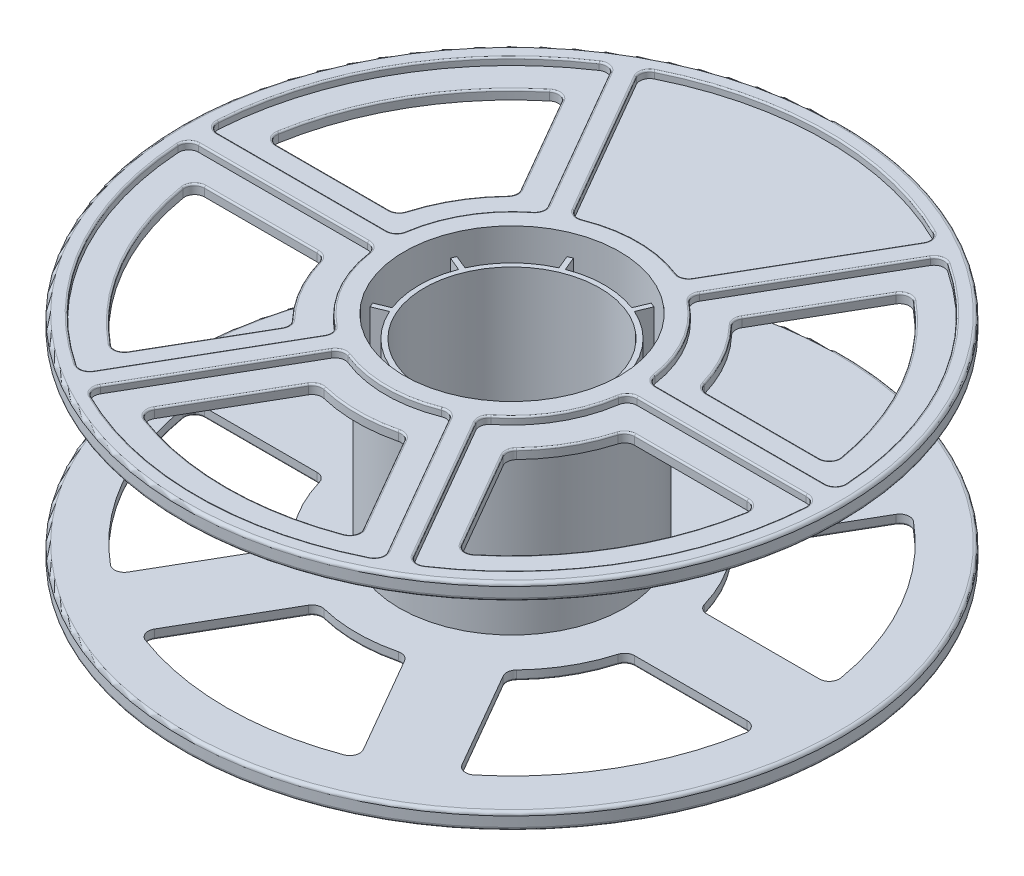
SolidWorks part; units mm, degrees
ref_plane "Front Plane" through (0, 0, 0) normal (0, 0, 1) x (1, 0, 0)
ref_plane "Top Plane" through (0, 0, 0) normal (0, 1, 0) x (1, 0, 0)
ref_plane "Right Plane" through (0, 0, 0) normal (1, 0, 0) x (0, 0, -1)
sketch "Sketch2" plane through (0, 0, 0) normal (0, 0, 1) x (1, 0, 0)
  line L0 (26.5, -26) -> (26.5, 26)
  line L1 (26.5, 26) -> (28, 26)
  line L2 (26.5, -26) -> (28, -26)
  line L3 (28, 26) -> (28, -26)
  line L4 (0, 0) -> (26.5, 0) construction
  line L5 (0, -1000) -> (0, 49000) construction
  point P3 (26.5, 0)
  dimension "D1" = 26.5
  dimension "D2" = 1.5
  dimension "D3" = 52
revolve "Inner Ring" add sketch "Sketch2" angle 360 about L5
sketch "Sketch3" plane through (0, 26, 0) normal (0, 1, 0) x (1, 0, 0)
  line L0 (0, 0) -> (0, 32.5) construction
  line L3 (11.741, 30.3051) -> (10.0184, 26.1464)
  line L4 (0, 0) -> (12.4372, 30.0261) construction
  line L5 (13.1268, 29.7311) -> (11.4042, 25.5723)
  line L6 (9.9856, 26.0672) -> (11.3714, 25.4932) construction
  line L7 (29.7311, 13.1268) -> (25.5723, 11.4042)
  line L8 (30.3051, 11.741) -> (26.1464, 10.0184)
  line L9 (25.4932, 11.3714) -> (26.0672, 9.9856) construction
  line L10 (30.3051, -11.741) -> (26.1464, -10.0184)
  line L11 (29.7311, -13.1268) -> (25.5723, -11.4042)
  line L12 (26.0672, -9.9856) -> (25.4932, -11.3714) construction
  line L13 (13.1268, -29.7311) -> (11.4042, -25.5723)
  line L14 (11.741, -30.3051) -> (10.0184, -26.1464)
  line L15 (11.3714, -25.4932) -> (9.9856, -26.0672) construction
  line L16 (-11.741, -30.3051) -> (-10.0184, -26.1464)
  line L17 (-13.1268, -29.7311) -> (-11.4042, -25.5723)
  line L18 (-9.9856, -26.0672) -> (-11.3714, -25.4932) construction
  line L19 (-29.7311, -13.1268) -> (-25.5723, -11.4042)
  line L20 (-30.3051, -11.741) -> (-26.1464, -10.0184)
  line L21 (-25.4932, -11.3714) -> (-26.0672, -9.9856) construction
  line L22 (-30.3051, 11.741) -> (-26.1464, 10.0184)
  line L23 (-29.7311, 13.1268) -> (-25.5723, 11.4042)
  line L24 (-26.0672, 9.9856) -> (-25.4932, 11.3714) construction
  line L25 (-13.1268, 29.7311) -> (-11.4042, 25.5723)
  line L26 (-11.741, 30.3051) -> (-10.0184, 26.1464)
  line L27 (-11.3714, 25.4932) -> (-9.9856, 26.0672) construction
  circle A0 centre (0, 0) radius 32.5 construction
  circle A1 centre (0, 0) radius 28 construction
  circle A3 centre (0, 0) radius 28 construction
  arc A5 (11.741, 30.3051) -> (13.1268, 29.7311) centre (0, 0) cw
  arc A6 (10.0184, 26.1464) -> (11.4042, 25.5723) centre (0, 0) cw
  arc A7 (29.7311, 13.1268) -> (30.3051, 11.741) centre (0, 0) cw
  arc A8 (25.5723, 11.4042) -> (26.1464, 10.0184) centre (0, 0) cw
  arc A9 (30.3051, -11.741) -> (29.7311, -13.1268) centre (0, 0) cw
  arc A10 (26.1464, -10.0184) -> (25.5723, -11.4042) centre (0, 0) cw
  arc A11 (13.1268, -29.7311) -> (11.741, -30.3051) centre (0, 0) cw
  arc A12 (11.4042, -25.5723) -> (10.0184, -26.1464) centre (0, 0) cw
  arc A13 (-11.741, -30.3051) -> (-13.1268, -29.7311) centre (0, 0) cw
  arc A14 (-10.0184, -26.1464) -> (-11.4042, -25.5723) centre (0, 0) cw
  arc A15 (-29.7311, -13.1268) -> (-30.3051, -11.741) centre (0, 0) cw
  arc A16 (-25.5723, -11.4042) -> (-26.1464, -10.0184) centre (0, 0) cw
  arc A17 (-30.3051, 11.741) -> (-29.7311, 13.1268) centre (0, 0) cw
  arc A18 (-26.1464, 10.0184) -> (-25.5723, 11.4042) centre (0, 0) cw
  arc A19 (-13.1268, 29.7311) -> (-11.741, 30.3051) centre (0, 0) cw
  arc A20 (-11.4042, 25.5723) -> (-10.0184, 26.1464) centre (0, 0) cw
  point P15 (10.6785, 25.7802)
  point P26 (25.7802, 10.6785)
  point P33 (25.7802, -10.6785)
  point P40 (10.6785, -25.7802)
  point P47 (-10.6785, -25.7802)
  point P54 (-25.7802, -10.6785)
  point P61 (-25.7802, 10.6785)
  point P68 (-10.6785, 25.7802)
  dimension "D1" = 65
  dimension "D2" = 22.5
  dimension "D3" = 1.5
  dimension "D4" = 8
extrude "Inner Ring Ribs" add sketch "Sketch3" against normal up to surface (52 mm away) up to face at (28, -26, 0)
sketch "Sketch4" plane through (0, 0, 0) normal (0, 0, 1) x (1, 0, 0)
  line L0 (0, 0) -> (32.5, 0) construction
  line L1 (32.5, 32.5) -> (32.5, -32.5)
  line L3 (34, 27.5) -> (34, -27.5)
  line L6 (99.5, -32.5) -> (99.5, -27.5)
  line L7 (99.5, -27.5) -> (34, -27.5)
  line L8 (32.5, 32.5) -> (99.5, 32.5)
  line L9 (99.5, 32.5) -> (99.5, 27.5)
  line L10 (99.5, 27.5) -> (34, 27.5)
  line L11 (32.5, -32.5) -> (99.5, -32.5)
  line L12 (0, -1000) -> (0, 49000) construction
  point P6 (32.5, 0)
  dimension "D1" = 65
  dimension "D3" = 32.5
  dimension "D2" = 1.5
  dimension "D4" = 5
  dimension "D5" = 5
  dimension "D6" = 99.5
revolve "Spool Panels" add sketch "Sketch4" angle 360 about L12
sketch "Sketch5" plane through (0, 32.5, 0) normal (0, 1, 0) x (1, 0, 0)
  line L0 (0, 0) -> (0, 99.5) construction
  line L1 (0, 0) -> (49.75, 86.1695) construction
  line L2 (0, 0) -> (-49.75, 86.1695) construction
  line L3 (31.0626, 59.602) -> (36.0856, 56.702) construction
  line L4 (-41.7223, 66.4651) -> (-36.6993, 69.3651) construction
  line L6 (43.3437, 80.8735) -> (17.8257, 36.675)
  line L7 (-43.3437, 80.8735) -> (-17.8257, 36.675)
  line L19 (91.7104, 2.9) -> (40.6743, 2.9)
  line L20 (48.3667, 77.9735) -> (22.8486, 33.775)
  line L21 (48.3667, -77.9735) -> (22.8486, -33.775)
  line L22 (91.7104, -2.9) -> (40.6743, -2.9)
  line L23 (-43.3437, -80.8735) -> (-17.8257, -36.675)
  line L24 (43.3437, -80.8735) -> (17.8257, -36.675)
  line L25 (-91.7104, -2.9) -> (-40.6743, -2.9)
  line L26 (-48.3667, -77.9735) -> (-22.8486, -33.775)
  line L27 (-48.3667, 77.9735) -> (-22.8486, 33.775)
  line L28 (-91.7104, 2.9) -> (-40.6743, 2.9)
  circle A0 centre (0, 0) radius 32.5 construction
  circle A1 centre (0, 0) radius 32.5 construction
  arc A2 (14.1161, 35.3885) -> (-14.1161, 35.3885) centre (0, 0) ccw
  circle A3 centre (0, 0) radius 99.5 construction
  arc A6 (42.0758, 85.0626) -> (-42.0758, 85.0626) centre (0, 0) ccw
  arc A8 (-17.8257, 36.675) -> (-14.1161, 35.3885) centre (-15.2276, 38.175) ccw
  arc A9 (17.8257, 36.675) -> (14.1161, 35.3885) centre (15.2276, 38.175) cw
  arc A10 (43.3437, 80.8735) -> (42.0758, 85.0626) centre (40.7457, 82.3735) ccw
  arc A11 (-43.3437, 80.8735) -> (-42.0758, 85.0626) centre (-40.7457, 82.3735) cw
  circle A42 centre (0, 0) radius 99.5 construction
  arc A43 (91.7104, 2.9) -> (94.7042, 6.0926) centre (91.7104, 5.9) ccw
  arc A44 (40.6743, 2.9) -> (37.7054, 5.4693) centre (40.6743, 5.9) cw
  arc A45 (37.7054, 5.4693) -> (23.5893, 29.9192) centre (0, 0) ccw
  arc A46 (22.8486, 33.775) -> (23.5893, 29.9192) centre (25.4467, 32.275) ccw
  arc A47 (48.3667, 77.9735) -> (52.6285, 78.97) centre (50.9648, 76.4735) cw
  arc A48 (94.7042, 6.0926) -> (52.6285, 78.97) centre (0, 0) ccw
  arc A49 (48.3667, -77.9735) -> (52.6285, -78.97) centre (50.9648, -76.4735) ccw
  arc A50 (22.8486, -33.775) -> (23.5893, -29.9192) centre (25.4467, -32.275) cw
  arc A51 (23.5893, -29.9192) -> (37.7054, -5.4693) centre (0, 0) ccw
  arc A52 (40.6743, -2.9) -> (37.7054, -5.4693) centre (40.6743, -5.9) ccw
  arc A53 (91.7104, -2.9) -> (94.7042, -6.0926) centre (91.7104, -5.9) cw
  arc A54 (52.6285, -78.97) -> (94.7042, -6.0926) centre (0, 0) ccw
  arc A55 (-43.3437, -80.8735) -> (-42.0758, -85.0626) centre (-40.7457, -82.3735) ccw
  arc A56 (-17.8257, -36.675) -> (-14.1161, -35.3885) centre (-15.2276, -38.175) cw
  arc A57 (-14.1161, -35.3885) -> (14.1161, -35.3885) centre (0, 0) ccw
  arc A58 (17.8257, -36.675) -> (14.1161, -35.3885) centre (15.2276, -38.175) ccw
  arc A59 (43.3437, -80.8735) -> (42.0758, -85.0626) centre (40.7457, -82.3735) cw
  arc A60 (-42.0758, -85.0626) -> (42.0758, -85.0626) centre (0, 0) ccw
  arc A61 (-91.7104, -2.9) -> (-94.7042, -6.0926) centre (-91.7104, -5.9) ccw
  arc A62 (-40.6743, -2.9) -> (-37.7054, -5.4693) centre (-40.6743, -5.9) cw
  arc A63 (-37.7054, -5.4693) -> (-23.5893, -29.9192) centre (0, 0) ccw
  arc A64 (-22.8486, -33.775) -> (-23.5893, -29.9192) centre (-25.4467, -32.275) ccw
  arc A65 (-48.3667, -77.9735) -> (-52.6285, -78.97) centre (-50.9648, -76.4735) cw
  arc A66 (-94.7042, -6.0926) -> (-52.6285, -78.97) centre (0, 0) ccw
  arc A67 (-48.3667, 77.9735) -> (-52.6285, 78.97) centre (-50.9648, 76.4735) ccw
  arc A68 (-22.8486, 33.775) -> (-23.5893, 29.9192) centre (-25.4467, 32.275) cw
  arc A69 (-23.5893, 29.9192) -> (-37.7054, 5.4693) centre (0, 0) ccw
  arc A70 (-40.6743, 2.9) -> (-37.7054, 5.4693) centre (-40.6743, 5.9) ccw
  arc A71 (-91.7104, 2.9) -> (-94.7042, 6.0926) centre (-91.7104, 5.9) cw
  arc A72 (-52.6285, 78.97) -> (-94.7042, 6.0926) centre (0, 0) ccw
  point P14 (33.5741, 58.152)
  point P17 (-39.2108, 67.9151)
  point P39 (44.9164, 83.5974)
  dimension "D1" = 5.6
  dimension "D4" = 4.6
  dimension "D7" = 3
  dimension "D8" = 6
  dimension "D2" = 30
  dimension "D3" = 30
  dimension "D5" = 5.8
  dimension "D6" = 5.8
extrude "Top Panel Inset" cut sketch "Sketch5" against normal blind 2.2
sketch "Sketch7" plane through (0, -32.5, 0) normal (0, -1, 0) x (1, 0, 0)
  line L0 (0, 0) -> (0, 99.5) construction
  line L1 (0, 0) -> (49.75, 86.1695) construction
  line L2 (0, 0) -> (-49.75, 86.1695) construction
  line L3 (31.0626, 59.602) -> (36.0856, 56.702) construction
  line L4 (-41.7223, 66.4651) -> (-36.6993, 69.3651) construction
  line L5 (43.3437, 80.8735) -> (17.8257, 36.675)
  line L6 (-43.3437, 80.8735) -> (-17.8257, 36.675)
  line L7 (91.7104, 2.9) -> (40.6743, 2.9)
  line L8 (48.3667, 77.9735) -> (22.8486, 33.775)
  line L9 (48.3667, -77.9735) -> (22.8486, -33.775)
  line L10 (91.7104, -2.9) -> (40.6743, -2.9)
  line L11 (-43.3437, -80.8735) -> (-17.8257, -36.675)
  line L12 (43.3437, -80.8735) -> (17.8257, -36.675)
  line L13 (-91.7104, -2.9) -> (-40.6743, -2.9)
  line L14 (-48.3667, -77.9735) -> (-22.8486, -33.775)
  line L15 (-48.3667, 77.9735) -> (-22.8486, 33.775)
  line L16 (-91.7104, 2.9) -> (-40.6743, 2.9)
  circle A0 centre (0, 0) radius 32.5 construction
  arc A1 (14.1161, 35.3885) -> (-14.1161, 35.3885) centre (0, 0) ccw
  arc A2 (42.0758, 85.0626) -> (-42.0758, 85.0626) centre (0, 0) ccw
  arc A3 (-17.8257, 36.675) -> (-14.1161, 35.3885) centre (-15.2276, 38.175) ccw
  arc A4 (17.8257, 36.675) -> (14.1161, 35.3885) centre (15.2276, 38.175) cw
  arc A5 (43.3437, 80.8735) -> (42.0758, 85.0626) centre (40.7457, 82.3735) ccw
  arc A6 (-43.3437, 80.8735) -> (-42.0758, 85.0626) centre (-40.7457, 82.3735) cw
  circle A7 centre (0, 0) radius 99.5 construction
  arc A8 (91.7104, 2.9) -> (94.7042, 6.0926) centre (91.7104, 5.9) ccw
  arc A9 (40.6743, 2.9) -> (37.7054, 5.4693) centre (40.6743, 5.9) cw
  arc A10 (37.7054, 5.4693) -> (23.5893, 29.9192) centre (0, 0) ccw
  arc A11 (22.8486, 33.775) -> (23.5893, 29.9192) centre (25.4467, 32.275) ccw
  arc A12 (48.3667, 77.9735) -> (52.6285, 78.97) centre (50.9648, 76.4735) cw
  arc A13 (94.7042, 6.0926) -> (52.6285, 78.97) centre (0, 0) ccw
  arc A14 (48.3667, -77.9735) -> (52.6285, -78.97) centre (50.9648, -76.4735) ccw
  arc A15 (22.8486, -33.775) -> (23.5893, -29.9192) centre (25.4467, -32.275) cw
  arc A16 (23.5893, -29.9192) -> (37.7054, -5.4693) centre (0, 0) ccw
  arc A17 (40.6743, -2.9) -> (37.7054, -5.4693) centre (40.6743, -5.9) ccw
  arc A18 (91.7104, -2.9) -> (94.7042, -6.0926) centre (91.7104, -5.9) cw
  arc A19 (52.6285, -78.97) -> (94.7042, -6.0926) centre (0, 0) ccw
  arc A20 (-43.3437, -80.8735) -> (-42.0758, -85.0626) centre (-40.7457, -82.3735) ccw
  arc A21 (-17.8257, -36.675) -> (-14.1161, -35.3885) centre (-15.2276, -38.175) cw
  arc A22 (-14.1161, -35.3885) -> (14.1161, -35.3885) centre (0, 0) ccw
  arc A23 (17.8257, -36.675) -> (14.1161, -35.3885) centre (15.2276, -38.175) ccw
  arc A24 (43.3437, -80.8735) -> (42.0758, -85.0626) centre (40.7457, -82.3735) cw
  arc A25 (-42.0758, -85.0626) -> (42.0758, -85.0626) centre (0, 0) ccw
  arc A26 (-91.7104, -2.9) -> (-94.7042, -6.0926) centre (-91.7104, -5.9) ccw
  arc A27 (-40.6743, -2.9) -> (-37.7054, -5.4693) centre (-40.6743, -5.9) cw
  arc A28 (-37.7054, -5.4693) -> (-23.5893, -29.9192) centre (0, 0) ccw
  arc A29 (-22.8486, -33.775) -> (-23.5893, -29.9192) centre (-25.4467, -32.275) ccw
  arc A30 (-48.3667, -77.9735) -> (-52.6285, -78.97) centre (-50.9648, -76.4735) cw
  arc A31 (-94.7042, -6.0926) -> (-52.6285, -78.97) centre (0, 0) ccw
  arc A32 (-48.3667, 77.9735) -> (-52.6285, 78.97) centre (-50.9648, 76.4735) ccw
  arc A33 (-22.8486, 33.775) -> (-23.5893, 29.9192) centre (-25.4467, 32.275) cw
  arc A34 (-23.5893, 29.9192) -> (-37.7054, 5.4693) centre (0, 0) ccw
  arc A35 (-40.6743, 2.9) -> (-37.7054, 5.4693) centre (-40.6743, 5.9) ccw
  arc A36 (-91.7104, 2.9) -> (-94.7042, 6.0926) centre (-91.7104, 5.9) cw
  arc A37 (-52.6285, 78.97) -> (-94.7042, 6.0926) centre (0, 0) ccw
  point P11 (33.5741, 58.152)
  point P14 (-39.2108, 67.9151)
extrude "Bottom Panel Inset" cut sketch "Sketch7" against normal blind 2.2
sketch "Sketch8" plane through (0, 30.3, 0) normal (0, 1, 0) x (1, 0, 0)
  line L0 (17.8257, 36.675) -> (43.3437, 80.8735) construction
  line L1 (-43.3437, 80.8735) -> (-17.8257, 36.675) construction
  line L2 (17.8257, 36.675) -> (43.3437, 80.8735) construction
  line L3 (-43.3437, 80.8735) -> (-17.8257, 36.675) construction
  line L4 (-31.5249, 76.4028) -> (-14.5228, 46.9542)
  line L5 (14.5228, 46.9542) -> (31.5249, 76.4028)
  line L6 (-36.4155, 84.8735) -> (-10.8975, 40.675) construction
  line L7 (10.8975, 40.675) -> (36.4155, 84.8735) construction
  line L8 (50.4043, 65.5028) -> (33.4021, 36.0542)
  line L9 (47.9249, 10.9) -> (81.9292, 10.9)
  line L10 (81.9292, -10.9) -> (47.9249, -10.9)
  line L11 (33.4021, -36.0542) -> (50.4043, -65.5028)
  line L12 (31.5249, -76.4028) -> (14.5228, -46.9542)
  line L13 (-14.5228, -46.9542) -> (-31.5249, -76.4028)
  line L14 (-50.4043, -65.5028) -> (-33.4021, -36.0542)
  line L15 (-47.9249, -10.9) -> (-81.9292, -10.9)
  line L16 (-81.9292, 10.9) -> (-47.9249, 10.9)
  line L17 (-33.4021, 36.0542) -> (-50.4043, 65.5028)
  arc A0 (42.0758, 85.0626) -> (-42.0758, 85.0626) centre (0, 0) ccw construction
  arc A1 (14.1161, 35.3885) -> (-14.1161, 35.3885) centre (0, 0) ccw construction
  arc A2 (42.0758, 85.0626) -> (-42.0758, 85.0626) centre (0, 0) ccw construction
  arc A3 (14.1161, 35.3885) -> (-14.1161, 35.3885) centre (0, 0) ccw construction
  arc A4 (11.2078, 45.5411) -> (-11.2078, 45.5411) centre (0, 0) ccw
  arc A5 (29.9712, 80.7152) -> (-29.9712, 80.7152) centre (0, 0) ccw
  arc A6 (38.1741, 77.1748) -> (-38.1741, 77.1748) centre (0, 0) ccw construction
  arc A7 (17.3765, 43.5622) -> (-17.3765, 43.5622) centre (0, 0) ccw construction
  arc A8 (-14.5228, 46.9542) -> (-11.2078, 45.5411) centre (-11.9247, 48.4542) ccw
  arc A9 (11.2078, 45.5411) -> (14.5228, 46.9542) centre (11.9247, 48.4542) ccw
  arc A10 (31.5249, 76.4028) -> (29.9712, 80.7152) centre (28.9269, 77.9028) ccw
  arc A11 (-29.9712, 80.7152) -> (-31.5249, 76.4028) centre (-28.9269, 77.9028) ccw
  arc A12 (54.9158, 66.3134) -> (50.4043, 65.5028) centre (53.0024, 64.0028) ccw
  arc A13 (33.4021, 36.0542) -> (33.8359, 32.4768) centre (36.0002, 34.5542) ccw
  arc A14 (45.0437, 13.0643) -> (33.8359, 32.4768) centre (0, 0) ccw
  arc A15 (45.0437, 13.0643) -> (47.9249, 10.9) centre (47.9249, 13.9) ccw
  arc A16 (81.9292, 10.9) -> (84.887, 14.4018) centre (81.9292, 13.9) ccw
  arc A17 (84.887, 14.4018) -> (54.9158, 66.3134) centre (0, 0) ccw
  arc A18 (84.887, -14.4018) -> (81.9292, -10.9) centre (81.9292, -13.9) ccw
  arc A19 (47.9249, -10.9) -> (45.0437, -13.0643) centre (47.9249, -13.9) ccw
  arc A20 (33.8359, -32.4768) -> (45.0437, -13.0643) centre (0, 0) ccw
  arc A21 (33.8359, -32.4768) -> (33.4021, -36.0542) centre (36.0002, -34.5542) ccw
  arc A22 (50.4043, -65.5028) -> (54.9158, -66.3134) centre (53.0024, -64.0028) ccw
  arc A23 (54.9158, -66.3134) -> (84.887, -14.4018) centre (0, 0) ccw
  arc A24 (29.9712, -80.7152) -> (31.5249, -76.4028) centre (28.9269, -77.9028) ccw
  arc A25 (14.5228, -46.9542) -> (11.2078, -45.5411) centre (11.9247, -48.4542) ccw
  arc A26 (-11.2078, -45.5411) -> (11.2078, -45.5411) centre (0, 0) ccw
  arc A27 (-11.2078, -45.5411) -> (-14.5228, -46.9542) centre (-11.9247, -48.4542) ccw
  arc A28 (-31.5249, -76.4028) -> (-29.9712, -80.7152) centre (-28.9269, -77.9028) ccw
  arc A29 (-29.9712, -80.7152) -> (29.9712, -80.7152) centre (0, 0) ccw
  arc A30 (-54.9158, -66.3134) -> (-50.4043, -65.5028) centre (-53.0024, -64.0028) ccw
  arc A31 (-33.4021, -36.0542) -> (-33.8359, -32.4768) centre (-36.0002, -34.5542) ccw
  arc A32 (-45.0437, -13.0643) -> (-33.8359, -32.4768) centre (0, 0) ccw
  arc A33 (-45.0437, -13.0643) -> (-47.9249, -10.9) centre (-47.9249, -13.9) ccw
  arc A34 (-81.9292, -10.9) -> (-84.887, -14.4018) centre (-81.9292, -13.9) ccw
  arc A35 (-84.887, -14.4018) -> (-54.9158, -66.3134) centre (0, 0) ccw
  arc A36 (-84.887, 14.4018) -> (-81.9292, 10.9) centre (-81.9292, 13.9) ccw
  arc A37 (-47.9249, 10.9) -> (-45.0437, 13.0643) centre (-47.9249, 13.9) ccw
  arc A38 (-33.8359, 32.4768) -> (-45.0437, 13.0643) centre (0, 0) ccw
  arc A39 (-33.8359, 32.4768) -> (-33.4021, 36.0542) centre (-36.0002, 34.5542) ccw
  arc A40 (-50.4043, 65.5028) -> (-54.9158, 66.3134) centre (-53.0024, 64.0028) ccw
  arc A41 (-54.9158, 66.3134) -> (-84.887, 14.4018) centre (0, 0) ccw
  dimension "D4" = 3
  dimension "D1" = 8
  dimension "D2" = 8.8
  dimension "D3" = 8.8
  dimension "D5" = 6
extrude "Panel Cutouts" cut sketch "Sketch8" against normal through all contours L8 A13 A14 A15 L9 A16 A17 A12 | L10 A19 A20 A21 L11 A22 A23 A18 | L12 A25 A26 A27 L13 A28 A29 A24 | L14 A31 A32 A33 L15 A34 A35 A30 | L16 A37 A38 A39 L17 A40 A41 A36
fillet "Upper Edge Fillet" radius 0.5 96 edges at (93.8988, 32.5, 3.8479) (82.1858, 32.5, 47.45) (50.2818, 32.5, 79.3948) (35.6077, 32.5, 55.8743) (22.5006, 32.5, 31.7091) (32.9956, 32.5, 19.05) (38.7112, 32.5, 3.6315) (-16.2106, 32.5, 35.3406) (0, 32.5, 38.1) (16.2106, 32.5, 35.3406) (30.5847, 32.5, 58.7743) (43.617, 32.5, 83.2427) (0, 32.5, 94.9) (-43.617, 32.5, 83.2427) (-38.7112, 32.5, 3.6315) (-32.9956, 32.5, 19.05) (-22.5006, 32.5, 31.7091) (-35.6077, 32.5, 55.8743) (-50.2818, 32.5, 79.3948) (-82.1858, 32.5, 47.45) (-93.8988, 32.5, 3.8479) (50.2818, 32.5, -79.3948) (82.1858, 32.5, -47.45) (93.8988, 32.5, -3.8479) (66.1924, 32.5, -2.9) (38.7112, 32.5, -3.6315) (32.9956, 32.5, -19.05) (22.5006, 32.5, -31.7091) (43.617, 32.5, -83.2427) (30.5847, 32.5, -58.7743) (16.2106, 32.5, -35.3406) (0, 32.5, -38.1) (-16.2106, 32.5, -35.3406) (-30.5847, 32.5, -58.7743) (-43.617, 32.5, -83.2427) (-50.2818, 32.5, -79.3948) (-35.6077, 32.5, -55.8743) (-22.5006, 32.5, -31.7091) (-32.9956, 32.5, -19.05) (-38.7112, 32.5, -3.6315) (-66.1924, 32.5, -2.9) (-93.8988, 32.5, -3.8479) (66.1924, 32.5, 2.9) (-30.5847, 32.5, 58.7743) (-66.1924, 32.5, 2.9) (35.6077, 32.5, -55.8743) (0, 32.5, -94.9) (-82.1858, 32.5, -47.45) (-38.7112, -32.5, 3.6315) (-66.1924, -32.5, 2.9) (-93.8988, -32.5, 3.8479) (-82.1858, -32.5, 47.45) (-50.2818, -32.5, 79.3948) (-35.6077, -32.5, 55.8743) (-22.5006, -32.5, 31.7091) (-22.5006, -32.5, -31.7091) (-35.6077, -32.5, -55.8743) (-50.2818, -32.5, -79.3948) (-82.1858, -32.5, -47.45) (-93.8988, -32.5, -3.8479) (-66.1924, -32.5, -2.9) (-38.7112, -32.5, -3.6315) (43.617, -32.5, -83.2427) (0, -32.5, -94.9) (-43.617, -32.5, -83.2427) (-30.5847, -32.5, -58.7743) (-16.2106, -32.5, -35.3406) (0, -32.5, -38.1) (16.2106, -32.5, -35.3406) (93.8988, -32.5, 3.8479) (66.1924, -32.5, 2.9) (38.7112, -32.5, 3.6315) (32.9956, -32.5, 19.05) (22.5006, -32.5, 31.7091) (35.6077, -32.5, 55.8743) (50.2818, -32.5, 79.3948) (16.2106, -32.5, 35.3406) (0, -32.5, 38.1) (-16.2106, -32.5, 35.3406) (-30.5847, -32.5, 58.7743) (-43.617, -32.5, 83.2427) (0, -32.5, 94.9) (43.617, -32.5, 83.2427) (50.2818, -32.5, -79.3948) (35.6077, -32.5, -55.8743) (22.5006, -32.5, -31.7091) (32.9956, -32.5, -19.05) (38.7112, -32.5, -3.6315) (66.1924, -32.5, -2.9) (93.8988, -32.5, -3.8479) (-32.9956, -32.5, 19.05) (-32.9956, -32.5, -19.05) (30.5847, -32.5, -58.7743) (82.1858, -32.5, 47.45) (30.5847, -32.5, 58.7743) (82.1858, -32.5, -47.45)
fillet "Outer Ring Fillet" radius 1 4 edges at (99.5, -27.5, 0) (99.5, 27.5, 0) (99.5, -32.5, 0) (99.5, 32.5, 0)
fillet "Panel Inset Fillet" radius 0.5 80 edges at (-84.2211, -30.3, 11.9642) (-74.5648, -30.3, 43.05) (-52.4719, -30.3, 66.9555) (-41.9032, -30.3, 50.7785) (-33.022, -30.3, 34.1931) (-40.6166, -30.3, 23.45) (-46.1231, -30.3, 11.5014) (-52.4719, -30.3, -66.9555) (-74.5648, -30.3, -43.05) (-84.2211, -30.3, -11.9642) (-64.9271, -30.3, -10.9) (-46.1231, -30.3, -11.5014) (-40.6166, -30.3, -23.45) (-33.022, -30.3, -34.1931) (13.1011, -30.3, 45.6945) (0, -30.3, 46.9) (-13.1011, -30.3, 45.6945) (-23.0239, -30.3, 61.6785) (-31.7493, -30.3, 78.9197) (0, -30.3, 86.1) (31.7493, -30.3, 78.9197) (46.1231, -30.3, 11.5014) (40.6166, -30.3, 23.45) (33.022, -30.3, 34.1931) (41.9032, -30.3, 50.7785) (52.4719, -30.3, 66.9555) (74.5648, -30.3, 43.05) (84.2211, -30.3, 11.9642) (52.4719, -30.3, -66.9555) (41.9032, -30.3, -50.7785) (33.022, -30.3, -34.1931) (40.6166, -30.3, -23.45) (46.1231, -30.3, -11.5014) (64.9271, -30.3, -10.9) (84.2211, -30.3, -11.9642) (-13.1011, 30.3, 45.6945) (-23.0239, 30.3, 61.6785) (-31.7493, 30.3, 78.9197) (0, 30.3, 86.1) (31.7493, 30.3, 78.9197) (23.0239, 30.3, 61.6785) (13.1011, 30.3, 45.6945) (-46.1231, 30.3, 11.5014) (-40.6166, 30.3, 23.45) (-33.022, 30.3, 34.1931) (-41.9032, 30.3, 50.7785) (-52.4719, 30.3, 66.9555) (-74.5648, 30.3, 43.05) (-84.2211, 30.3, 11.9642) (84.2211, 30.3, 11.9642) (74.5648, 30.3, 43.05) (52.4719, 30.3, 66.9555) (41.9032, 30.3, 50.7785) (33.022, 30.3, 34.1931) (40.6166, 30.3, 23.45) (46.1231, 30.3, 11.5014) (-33.022, 30.3, -34.1931) (-40.6166, 30.3, -23.45) (-46.1231, 30.3, -11.5014) (-64.9271, 30.3, -10.9) (-84.2211, 30.3, -11.9642) (-74.5648, 30.3, -43.05) (-52.4719, 30.3, -66.9555) (52.4719, 30.3, -66.9555) (74.5648, 30.3, -43.05) (84.2211, 30.3, -11.9642) (64.9271, 30.3, -10.9) (46.1231, 30.3, -11.5014) (40.6166, 30.3, -23.45) (33.022, 30.3, -34.1931) (-64.9271, -30.3, 10.9) (-41.9032, -30.3, -50.7785) (23.0239, -30.3, 61.6785) (64.9271, -30.3, 10.9) (74.5648, -30.3, -43.05) (0, 30.3, 46.9) (-64.9271, 30.3, 10.9) (64.9271, 30.3, 10.9) (-41.9032, 30.3, -50.7785) (41.9032, 30.3, -50.7785)
equation "\"Spool_Outer_Diameter\"=199"
equation "\"Spool_Inner_Diameter_1\"= 53"
equation "\"Spool_Inner_Diameter_2\"= 65"
equation "\"Spool_Height\"= 65"
equation "\"Spool_Panel_Height\"= 5"
equation "\"D1@Sketch2\"=\"Spool_Inner_Diameter_1\" / 2"
equation "\"Spool_Inner_Height\"= 52"
equation "\"D3@Sketch2\"=\"Spool_Inner_Height\""
equation "\"D1@Sketch3\"=\"Spool_Inner_Diameter_2\""
equation "\"D1@Sketch4\"=\"Spool_Height\""
equation "\"D3@Sketch4\"=\"Spool_Inner_Diameter_2\" / 2"
equation "\"D6@Sketch4\"=\"Spool_Outer_Diameter\" / 2"
